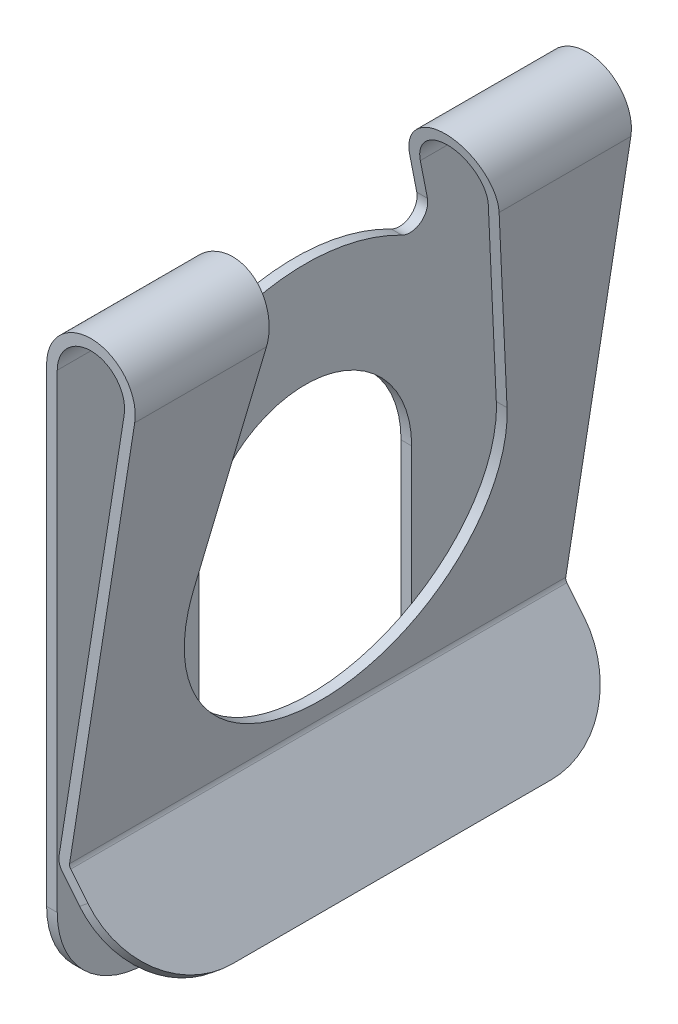
SolidWorks part; units mm, degrees
ref_plane "Front Plane" through (0, 0, 0) normal (0, 0, 1) x (1, 0, 0)
ref_plane "Top Plane" through (0, 0, 0) normal (0, 1, 0) x (1, 0, 0)
ref_plane "Right Plane" through (0, 0, 0) normal (1, 0, 0) x (0, 0, -1)
ref_plane "Plane1" through (0, 0, 0) normal (0, 0, 1) x (1, 0, 0)
sketch "Sketch1" plane through (0, 0, 0) normal (0, 0, 1) x (1, 0, 0)
  line L0 (0, 13.7) -> (0, -17.8)
  line L1 (0, -17.8) -> (0.6, -17.8)
  line L2 (0.6, -17.8) -> (0.6, 13.7)
  line L3 (4.377, 13.4051) -> (0.7039, -9.9743)
  line L4 (0.895, -10.6822) -> (5.0363, -15.7685)
  line L5 (5.0363, -15.7685) -> (5.5016, -15.3897)
  line L6 (5.5016, -15.3897) -> (1.3603, -10.3034)
  line L7 (1.2966, -10.0674) -> (4.9697, 13.312)
  arc A0 (0.6, 13.7) -> (4.377, 13.4051) centre (2.5, 13.7) cw
  arc A1 (0.7039, -9.9743) -> (0.895, -10.6822) centre (1.593, -10.114) ccw
  arc A2 (1.3603, -10.3034) -> (1.2966, -10.0674) centre (1.593, -10.114) cw
  arc A3 (4.9697, 13.312) -> (0, 13.7) centre (2.5, 13.7) ccw
extrude "Boss-Extrude1" add sketch "Sketch1" against normal blind 14 and the other way blind 14
ref_plane "Plane2" through (0, 0, 0) normal (1, 0, 0) x (0, 0, -1)
sketch "Sketch2" plane through (0, 0, 0) normal (1, 0, 0) x (0, 0, -1)
  line L0 (-6, 0) -> (-6, -17.8)
  line L1 (-6, -17.8) -> (6, -17.8)
  line L2 (6, -17.8) -> (6, 0)
  arc A0 (6, 0) -> (-6, 0) centre (0, 0) ccw
extrude "Cut-Extrude1" cut sketch "Sketch2" along normal blind 0.6
ref_plane "Plane3" through (0.6, 0, 0) normal (1, 0, 0) x (0, 0, -1)
sketch "Sketch3" plane through (0.6, 0, 0) normal (1, 0, 0) x (0, 0, -1)
  line L0 (8.8324, 1.7287) -> (6, 16.2)
  line L1 (6, 16.2) -> (-6, 16.2)
  line L2 (-6, 16.2) -> (-8.8324, 1.7287)
  arc A0 (-8.8324, 1.7287) -> (8.8324, 1.7287) centre (0, 0) ccw
extrude "Cut-Extrude2" cut sketch "Sketch3" along normal blind 5.4
ref_plane "Plane4" through (0.6, 0, 0) normal (1, 0, 0) x (0, 0, -1)
sketch "Sketch4" plane through (0.6, 0, 0) normal (1, 0, 0) x (0, 0, -1)
  line L0 (6.8886, 11.6601) -> (6, 16.2)
  line L1 (6, 16.2) -> (-6, 16.2)
  line L2 (-6, 16.2) -> (-6.8886, 11.6601)
  arc A0 (-6.8886, 11.6601) -> (-5.4493, 10.579) centre (-5.9072, 11.468) ccw
  arc A1 (-5.4493, 10.579) -> (5.4493, 10.579) centre (0, 0) cw
  arc A2 (5.4493, 10.579) -> (6.8886, 11.6601) centre (5.9072, 11.468) ccw
extrude "Cut-Extrude3" cut sketch "Sketch4" against normal blind 5.4
ref_plane "Plane5" through (0, 0, 0) normal (1, 0, 0) x (0, 0, -1)
sketch "Sketch5" plane through (0, 0, 0) normal (1, 0, 0) x (0, 0, -1)
  line L0 (-14, -17.8) -> (-9, -17.8)
  line L1 (-14, -12.8) -> (-14, -17.8)
  arc A0 (-9, -17.8) -> (-14, -12.8) centre (-9, -12.8) cw
extrude "Cut-Extrude4" cut sketch "Sketch5" along normal blind 0.6
ref_plane "Plane6" through (0, 0, 0) normal (1, 0, 0) x (0, 0, -1)
sketch "Sketch6" plane through (0, 0, 0) normal (1, 0, 0) x (0, 0, -1)
  line L0 (9, -17.8) -> (14, -17.8)
  line L1 (14, -17.8) -> (14, -12.8)
  arc A0 (14, -12.8) -> (9, -17.8) centre (9, -12.8) cw
extrude "Cut-Extrude5" cut sketch "Sketch6" along normal blind 0.6
ref_plane "Plane7" through (0, 0, 0) normal (1, 0, 0) x (0, 0, -1)
sketch "Sketch7" plane through (0, 0, 0) normal (1, 0, 0) x (0, 0, -1)
  line L0 (6, -17.8) -> (7, -17.8)
  line L1 (6, -16.8) -> (6, -17.8)
  arc A0 (7, -17.8) -> (6, -16.8) centre (7, -16.8) cw
extrude "Cut-Extrude6" cut sketch "Sketch7" along normal blind 0.6
ref_plane "Plane8" through (0, 0, 0) normal (1, 0, 0) x (0, 0, -1)
sketch "Sketch8" plane through (0, 0, 0) normal (1, 0, 0) x (0, 0, -1)
  line L0 (-7, -17.8) -> (-6, -17.8)
  line L1 (-6, -17.8) -> (-6, -16.8)
  arc A0 (-6, -16.8) -> (-7, -17.8) centre (-7, -16.8) cw
extrude "Cut-Extrude7" cut sketch "Sketch8" along normal blind 0.6
ref_plane "Plane9" through (-4.2267, -3.4414, 0) normal (0.7755, 0.6314, 0) x (0, 0, -1)
sketch "Sketch9" plane through (-4.2267, -3.4414, 0) normal (0.7755, 0.6314, 0) x (0, 0, -1)
  line L0 (-14, -10.3809) -> (-19, -10.3809)
  line L1 (-19, -10.3809) -> (-19, -20.3809)
  line L2 (-19, -20.3809) -> (19, -20.3809)
  line L3 (19, -20.3809) -> (19, -10.3809)
  line L4 (19, -10.3809) -> (14, -10.3809)
  line L5 (9, -15.3809) -> (-9, -15.3809)
  arc A0 (14, -10.3809) -> (9, -15.3809) centre (9, -10.3809) cw
  arc A1 (-9, -15.3809) -> (-14, -10.3809) centre (-9, -10.3809) cw
extrude "Cut-Extrude8" cut sketch "Sketch9" against normal blind 1.2 and the other way blind 1.2
